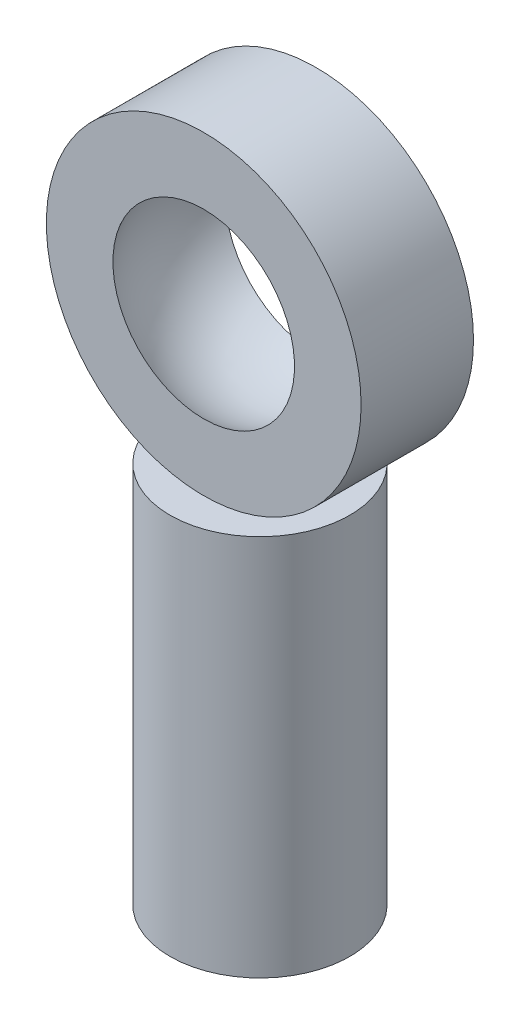
SolidWorks part; units mm, degrees
material "3.1355 (EN-AW 2024)"
ref_plane "Спереди" through (0, 0, 0) normal (0, 0, 1) x (1, 0, 0)
ref_plane "Сверху" through (0, 0, 0) normal (0, 1, 0) x (1, 0, 0)
ref_plane "Справа" through (0, 0, 0) normal (1, 0, 0) x (0, 0, -1)
sketch "Эскиз1" plane through (0, 0, 0) normal (0, 0, 1) x (1, 0, 0)
  circle A0 centre (0, 0) radius 7
  dimension "D1" = 14
extrude "Бобышка-Вытянуть1" add sketch "Эскиз1" along normal blind 2.5 and the other way blind 2.5
sketch3d "Трехмерный эскиз2" plane through (0, 0, 0) normal (0, 0, 1) x (1, 0, 0)
  dimension "D1" = 7
sketch "Эскиз4" plane through (0, -7, 0) normal (0, 1, 0) x (1, 0, 0)
  circle A0 centre (0, 0) radius 4
  dimension "D1" = 8
extrude "Выступ под шпильку" add sketch "Эскиз4" against normal blind 17 separate body
sketch "Эскиз5" plane through (0, -24, 0) normal (0, -1, 0) x (1, 0, 0)
  circle A0 centre (0, 0) radius 2
  dimension "D1" = 4
extrude "Углубление под шпильку" cut sketch "Эскиз5" against normal blind 12
sketch "Эскиз8" plane through (0, 0, 0) normal (1, 0, 0) x (0, 0, -1)
  line L0 (-3.5, 0) -> (0, 0) construction
  line L1 (-3.5, 0) -> (3.5, 0)
  line L2 (-3.5, 0) -> (-3.5, 3.2113)
  line L3 (0, 0) -> (0, 4.75) construction
  line L4 (3.5, 0) -> (3.5, 3.2113)
  arc A0 (3.5, 3.2113) -> (-3.5, 3.2113) centre (0, 0) ccw
  dimension "D2" = 4.75
  dimension "D1" = 3.5
revolve "Вырез под шарнир" cut sketch "Эскиз8" angle 360 about L0
